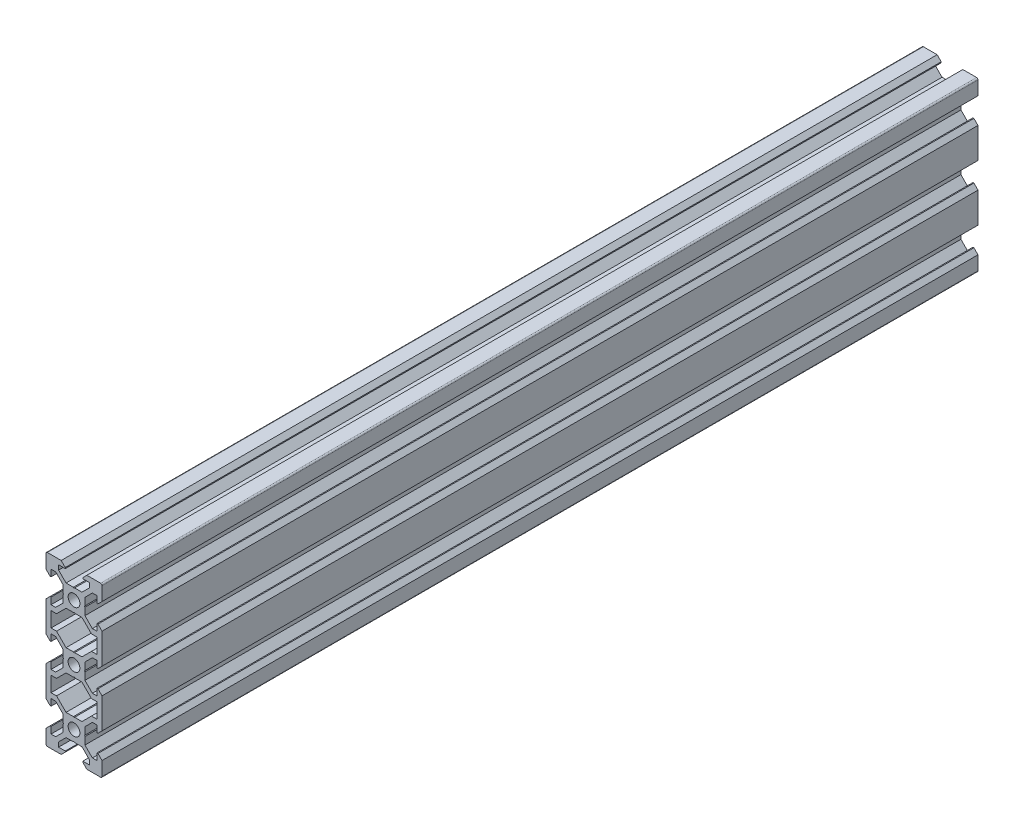
SolidWorks part; units mm, degrees
ref_plane "Plan de face" through (0, 0, 0) normal (0, 0, 1) x (1, 0, 0)
ref_plane "Plan de dessus" through (0, 0, 0) normal (0, 1, 0) x (1, 0, 0)
ref_plane "Plan de droite" through (0, 0, 0) normal (1, 0, 0) x (0, 0, -1)
ref_axis "Axe" through (0, 0, -13.782) along (0, 0, 1)
sketch "Esquisse1" plane through (0, 0, 0) normal (0, 0, 1) x (1, 0, 0)
  line L0 (0, 27.6392) -> (0, -27.6392) construction
  line L1 (-33.6074, 0) -> (33.6074, 0) construction
  line L2 (0, 0) -> (-22.2114, 22.2114) construction
  line L3 (-9.5, 10) -> (-4.58, 10)
  line L4 (-4.58, 10) -> (-3.125, 8.545)
  line L5 (-3.125, 8.545) -> (-3.125, 8.2)
  line L6 (-3.125, 8.2) -> (-5.5, 8.2)
  line L7 (-2.8393, 3.9) -> (-5.5, 6.5607)
  line L8 (-2.8393, 3.9) -> (-0.21, 3.9)
  line L9 (-5.5, 6.5607) -> (-5.5, 8.2)
  line L10 (0, 3.69) -> (0, 2.1)
  line L11 (-3.9, 2.8393) -> (-6.5607, 5.5)
  line L12 (-8.545, 3.125) -> (-8.2, 3.125)
  line L13 (-8.2, 3.125) -> (-8.2, 5.5)
  line L14 (-6.5607, 5.5) -> (-8.2, 5.5)
  line L15 (-10, 4.58) -> (-8.545, 3.125)
  line L16 (-10, 9.5) -> (-10, 4.58)
  line L17 (-0.21, 3.9) -> (0, 3.69)
  line L18 (-3.9, 2.8393) -> (-3.9, 0.21)
  line L19 (-6.2393, -12.7) -> (-8.2, -12.7)
  line L20 (-3.9, 0.21) -> (-3.69, 0)
  line L21 (-0.21, -3.9) -> (0, -3.69)
  line L22 (0, -3.69) -> (0, -2.1)
  line L23 (-6.5607, -5.5) -> (-8.2, -5.5)
  line L24 (-2.8393, -3.9) -> (-0.21, -3.9)
  line L25 (-8.545, -3.125) -> (-8.2, -3.125)
  line L26 (-10, -4.58) -> (-8.545, -3.125)
  line L27 (-8.2, -3.125) -> (-8.2, -5.5)
  line L28 (-2.8393, -3.9) -> (-6.2393, -7.3)
  line L29 (-3.9, -2.8393) -> (-6.5607, -5.5)
  line L30 (-3.9, -2.8393) -> (-3.9, -0.21)
  line L31 (-3.9, -0.21) -> (-3.69, 0)
  line L32 (-6.2393, -7.3) -> (-8.2, -7.3)
  line L33 (-8.2, -7.3) -> (-8.2, -12.7)
  line L34 (-8.2, -10) -> (-10, -10) construction
  line L35 (-10, -15.42) -> (-10, -4.58)
  line L36 (-3.9, -19.79) -> (-3.69, -20)
  line L37 (-3.9, -17.1607) -> (-3.9, -19.79)
  line L38 (-3.9, -17.1607) -> (-6.5607, -14.5)
  line L39 (-2.8393, -16.1) -> (-6.2393, -12.7)
  line L40 (-8.2, -16.875) -> (-8.2, -14.5)
  line L41 (-10, -15.42) -> (-8.545, -16.875)
  line L42 (-8.545, -16.875) -> (-8.2, -16.875)
  line L43 (-2.8393, -16.1) -> (-0.21, -16.1)
  line L44 (-6.5607, -14.5) -> (-8.2, -14.5)
  line L45 (0, -16.31) -> (0, -17.9)
  line L46 (-0.21, -16.1) -> (0, -16.31)
  line L47 (-8.2, -30) -> (-10, -30) construction
  line L48 (-3.69, -20) -> (0, -20) construction
  line L49 (-0.21, -23.9) -> (0, -23.69)
  line L50 (0, -23.69) -> (0, -22.1)
  line L51 (-6.5607, -25.5) -> (-8.2, -25.5)
  line L52 (-2.8393, -23.9) -> (-0.21, -23.9)
  line L53 (-8.545, -23.125) -> (-8.2, -23.125)
  line L54 (-10, -24.58) -> (-8.545, -23.125)
  line L55 (-8.2, -23.125) -> (-8.2, -25.5)
  line L56 (-2.8393, -23.9) -> (-6.2393, -27.3)
  line L57 (-3.9, -22.8393) -> (-6.5607, -25.5)
  line L58 (-3.9, -22.8393) -> (-3.9, -20.21)
  line L59 (-3.9, -20.21) -> (-3.69, -20)
  line L60 (-10, -24.58) -> (-10, -35.42)
  line L61 (-8.2, -32.7) -> (-8.2, -27.3)
  line L62 (-6.2393, -32.7) -> (-8.2, -32.7)
  line L63 (-3.9, -39.79) -> (-3.69, -40)
  line L64 (-3.9, -37.1607) -> (-3.9, -39.79)
  line L65 (-3.9, -37.1607) -> (-6.5607, -34.5)
  line L66 (-2.8393, -36.1) -> (-6.2393, -32.7)
  line L67 (-8.2, -36.875) -> (-8.2, -34.5)
  line L68 (-10, -35.42) -> (-8.545, -36.875)
  line L69 (-8.545, -36.875) -> (-8.2, -36.875)
  line L70 (-2.8393, -36.1) -> (-0.21, -36.1)
  line L71 (-6.5607, -34.5) -> (-8.2, -34.5)
  line L72 (0, -36.31) -> (0, -37.9)
  line L73 (-0.21, -36.1) -> (0, -36.31)
  line L74 (-3.9, -40.21) -> (-3.69, -40)
  line L75 (-6.2393, -27.3) -> (-8.2, -27.3)
  line L76 (-3.9, -42.8393) -> (-3.9, -40.21)
  line L77 (-0.21, -43.9) -> (0, -43.69)
  line L78 (-10, -49.5) -> (-10, -44.58)
  line L79 (-10, -44.58) -> (-8.545, -43.125)
  line L80 (-6.5607, -45.5) -> (-8.2, -45.5)
  line L81 (-8.2, -43.125) -> (-8.2, -45.5)
  line L82 (-8.545, -43.125) -> (-8.2, -43.125)
  line L83 (-3.9, -42.8393) -> (-6.5607, -45.5)
  line L84 (0, -43.69) -> (0, -42.1)
  line L85 (-5.5, -46.5607) -> (-5.5, -48.2)
  line L86 (-2.8393, -43.9) -> (-0.21, -43.9)
  line L87 (-2.8393, -43.9) -> (-5.5, -46.5607)
  line L88 (-3.125, -48.2) -> (-5.5, -48.2)
  line L89 (-3.125, -48.545) -> (-3.125, -48.2)
  line L90 (-4.58, -50) -> (-3.125, -48.545)
  line L91 (-9.5, -50) -> (-4.58, -50)
  arc A0 (0, -2.1) -> (0, 2.1) centre (0, 0) cw
  arc A1 (-9.5, 10) -> (-10, 9.5) centre (-9.5, 9.5) ccw
  arc A2 (0, -37.9) -> (0, -42.1) centre (0, -40) ccw
  arc A3 (-9.5, -50) -> (-10, -49.5) centre (-9.5, -49.5) cw
  arc A4 (0, -17.9) -> (0, -22.1) centre (0, -20) ccw
  point P4 (0, 0)
  point P7 (0, 0)
  point P30 (-10, 10)
  point P60 (0, -20)
  point P111 (-10, -50)
  dimension "D5" = 11
  dimension "D2" = 2.1
  dimension "D3" = 6.25
  dimension "D10" = 0.5
  dimension "D4" = 9.16
  dimension "D6" = 1.5
  dimension "D7" = 1.8
  dimension "D8" = 4.3
  dimension "D9" = 20
  dimension "D11" = 0.42
  dimension "D12" = 10
  dimension "D13" = 1.8
extrude "Boss.-Extru.1" add sketch "Esquisse1" along normal blind 312.76
sketch "Esquisse3" plane through (0, 0, 312.76) normal (0, 0, 1) x (1, 0, 0)
  line L0 (0, 0) -> (-9.8536, 9.8536) construction
  line L1 (-8.2, 8.2) -> (-8.2, 6.57)
  line L2 (-8.2, 6.57) -> (-7.54, 6.57)
  line L3 (-7.54, 6.57) -> (-6.57, 7.54)
  line L4 (-8.2, 3.125) -> (-8.2, 5.5) construction
  line L5 (-6.57, 8.2) -> (-6.57, 7.54)
  line L6 (-8.2, 8.2) -> (-6.57, 8.2)
  line L7 (-5.5, 6.5607) -> (-5.5, 8.2) construction
  line L8 (-3.69, -20) -> (0, -20) construction
  line L9 (-8.2, -48.2) -> (-6.57, -48.2)
  line L10 (-6.57, -48.2) -> (-6.57, -47.54)
  line L11 (-7.54, -46.57) -> (-6.57, -47.54)
  line L12 (-8.2, -46.57) -> (-7.54, -46.57)
  line L13 (-8.2, -48.2) -> (-8.2, -46.57)
  arc A0 (-9.5, 10) -> (-10, 9.5) centre (-9.5, 9.5) ccw construction
  point P13 (-7.055, 7.055)
  point P14 (-6.57, 7.87)
  point P26 (-7.055, -47.055)
  dimension "D1" = 1.07
extrude "Enlèv. mat.-Extru.1" [suppressed] cut sketch "Esquisse3" against normal through all
mirror "Symétrie1" about plane through (0, 3.69, 312.76) normal (-1, 0, 0) of "Enlèv. mat.-Extru.1", "Boss.-Extru.1"
